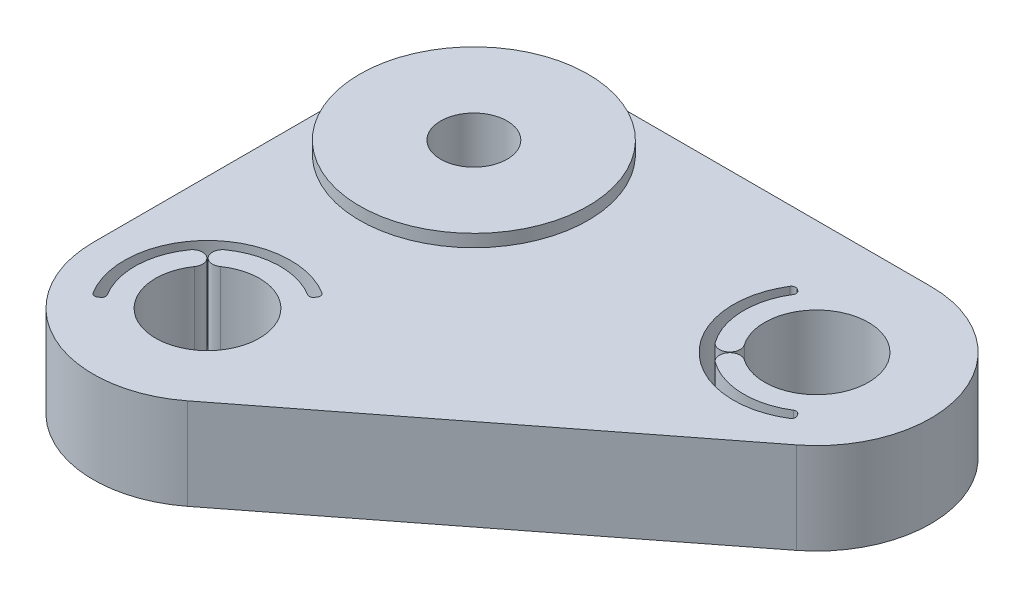
SolidWorks part; units mm, degrees
ref_plane "Front" through (0, 0, 0) normal (0, 0, 1) x (1, 0, 0)
ref_plane "Top" through (0, 0, 0) normal (0, 1, 0) x (1, 0, 0)
ref_plane "Right" through (0, 0, 0) normal (1, 0, 0) x (0, 0, -1)
sketch "Sketch2" plane through (0, 0, 0) normal (0, 1, 0) x (1, 0, 0)
  line L0 (0, 0) -> (0, 12.825) construction
  line L1 (0, 12.825) -> (16.5, 12.825) construction
  line L2 (-5.5, -11.241) -> (32.5382, 18.325) construction
  line L3 (32.5382, 18.325) -> (-5.5, 18.325) construction
  line L4 (-5.5, 18.325) -> (-5.5, -11.241) construction
  line L5 (-5.5, 0) -> (-5.5, 12.825)
  line L6 (0, 18.325) -> (16.5, 18.325)
  line L7 (19.8753, 8.4825) -> (3.3753, -4.3425)
  circle A0 centre (0, 12.825) radius 1.6
  circle A1 centre (16.5, 12.825) radius 2.5
  circle A2 centre (0, 0) radius 2.5
  circle A3 centre (16.5, 12.825) radius 5.5 construction
  circle A4 centre (0, 12.825) radius 5.5 construction
  circle A5 centre (0, 0) radius 5.5 construction
  arc A6 (-5.5, 12.825) -> (0, 18.325) centre (0, 12.825) cw
  arc A7 (16.5, 18.325) -> (19.8753, 8.4825) centre (16.5, 12.825) cw
  arc A8 (3.3753, -4.3425) -> (-5.5, 0) centre (0, 0) cw
  dimension "D3" = 5
  dimension "D4" = 3.2
  dimension "D5" = 3
  dimension "D1" = 12.825
  dimension "D2" = 16.5
extrude "Boss-Extrude1" add sketch "Sketch2" along normal blind 1.57
other "Move Face1" [suppressed] offset 0.0762 parameters "D1"=0.0762
sketch "Sketch3" plane through (0, 1.57, 0) normal (0, 1, 0) x (1, 0, 0)
  line L3 (3.3753, -4.3425) -> (19.8753, 8.4825)
  line L4 (16.5, 18.325) -> (0, 18.325)
  line L5 (-5.5, 12.825) -> (-5.5, 0)
  line L6 (3.3753, -4.3425) -> (19.8753, 8.4825)
  line L7 (16.5, 18.325) -> (0, 18.325)
  line L8 (-5.5, 12.825) -> (-5.5, 0)
  circle A0 centre (0, 0) radius 2.5 construction
  circle A1 centre (16.5, 12.825) radius 2.5 construction
  circle A2 centre (0, 12.825) radius 1.6 construction
  arc A3 (-5.5, 0) -> (3.3753, -4.3425) centre (0, 0) ccw
  arc A4 (19.8753, 8.4825) -> (16.5, 18.325) centre (16.5, 12.825) ccw
  arc A5 (0, 18.325) -> (-5.5, 12.825) centre (0, 12.825) ccw
  arc A6 (-5.5, 0) -> (3.3753, -4.3425) centre (0, 0) ccw
  arc A7 (19.8753, 8.4825) -> (16.5, 18.325) centre (16.5, 12.825) ccw
  arc A8 (0, 18.325) -> (-5.5, 12.825) centre (0, 12.825) ccw
  circle A9 centre (0, 0) radius 2.5
  circle A10 centre (16.5, 12.825) radius 2.5
  circle A11 centre (0, 12.825) radius 1.6
  dimension "D1" = 0
extrude "Boss-Extrude2" add sketch "Sketch3" along normal blind 2.83
sketch "Sketch4" plane through (0, 4.4, 0) normal (0, 1, 0) x (1, 0, 0)
  circle A8 centre (0, 12.825) radius 1.6 construction
  circle A9 centre (0, 12.825) radius 1.6
  circle A10 centre (0, 12.825) radius 5.5
  arc A11 (0, 18.325) -> (-5.5, 12.825) centre (0, 12.825) ccw construction
extrude "Boss-Extrude3" add sketch "Sketch4" along normal blind 0.6
sketch "Sketch5" plane through (0, 0, 0) normal (0, -1, 0) x (1, 0, 0)
  line B0 (13.4736, -14.9441) -> (13.3915, -15.0016)
  line B1 (18.6191, -9.7986) -> (18.6766, -9.7165)
  line B2 (14.0425, -11.1043) -> (16.5, -12.825) construction
  arc B3 (13.1072, -14.9437) -> (18.6187, -9.4322) centre (16.5, -12.825) cw
  arc B4 (14.4521, -11.3911) -> (13.633, -10.8175) centre (14.0425, -11.1043) ccw
  arc B5 (13.633, -10.8175) -> (13.5286, -14.6746) centre (16.5, -12.825) ccw
  arc B6 (14.4925, -9.958) -> (18.3496, -9.8536) centre (16.5, -12.825) cw
  arc B7 (15.0661, -10.7771) -> (14.4925, -9.958) centre (14.7793, -10.3675) cw
  arc B8 (14.4521, -11.3911) -> (15.0661, -10.7771) centre (16.5, -12.825) cw
  arc B9 (13.4736, -14.9441) -> (13.5286, -14.6746) centre (13.3589, -14.7803) ccw
  arc B10 (13.3915, -15.0016) -> (13.1072, -14.9437) centre (13.2768, -14.8377) cw
  arc B11 (18.6766, -9.7165) -> (18.6187, -9.4322) centre (18.5127, -9.6018) ccw
  arc B12 (18.6191, -9.7986) -> (18.3496, -9.8536) centre (18.4553, -9.6839) cw
  line B13 (0, 0) -> (-2.8284, -2.8284) construction
  line B14 (2.1191, -3.0264) -> (2.1766, -3.1085)
  line B15 (-3.0264, 2.1191) -> (-3.1085, 2.1766)
  line B16 (-1.7207, -2.4575) -> (0, 0) construction
  arc B17 (2.1187, -3.3928) -> (-3.3928, 2.1187) centre (0, 0) cw
  arc B18 (-1.4339, -2.0479) -> (-2.0075, -2.867) centre (-1.7207, -2.4575) ccw
  arc B19 (-2.0075, -2.867) -> (1.8496, -2.9714) centre (0, 0) ccw
  arc B20 (-2.867, -2.0075) -> (-2.9714, 1.8496) centre (0, 0) cw
  arc B21 (-2.0479, -1.4339) -> (-2.867, -2.0075) centre (-2.4575, -1.7207) cw
  arc B22 (-1.4339, -2.0479) -> (-2.0479, -1.4339) centre (0, 0) cw
  arc B23 (2.1191, -3.0264) -> (1.8496, -2.9714) centre (1.9553, -3.1411) ccw
  arc B24 (2.1766, -3.1085) -> (2.1187, -3.3928) centre (2.0127, -3.2232) cw
  arc B25 (-3.1085, 2.1766) -> (-3.3928, 2.1187) centre (-3.2232, 2.0127) ccw
  arc B26 (-3.0264, 2.1191) -> (-2.9714, 1.8496) centre (-3.1411, 1.9553) cw
sketch_block_instance "5mm_bore_flexure_relief-1"
sketch_block "5mm_bore_flexure_relief" parameters "D4"=2.5, "D6"=0.2, "D1"=80, "D2"=0.5, "D3"=70, "D5"=1
sketch_block_instance "5mm_bore_flexure_relief-2"
extrude "bore relief" cut sketch "Sketch5" against normal through all
sketch "Sketch6" plane through (0, 0, -18.325) normal (0, 0, -1) x (-1, 0, 0)
  line L0 (0, 3.8) -> (-16.5, 3.8) construction
  line L1 (0, 4.4) -> (0, 0) construction
  line L2 (-16.5, 4.4) -> (-16.5, 0) construction
  line L3 (-16.5, 4.4) -> (0, 4.4) construction
  text T0 "RXR-01" font "Century Gothic" height in points 12
  dimension "D1" = 0.6
extrude "Part Num Right" cut sketch "Sketch6" against normal blind 0.4
mirror "Mirror3" [suppressed] of bodies 106 104
delete or keep bodies "Body-Delete/Keep 1" [suppressed] type keep bodies bodies 105
sketch "Sketch7" [suppressed] plane through (0, 0, -18.325) normal (0, 0, -1) x (-1, 0, 0)
  line L0 (27.5, 3.8) -> (11, 3.8) construction
  line L1 (27.5, 4.4) -> (27.5, 0) construction
  line L2 (11, 4.4) -> (11, 0) construction
  line L3 (27.5, 4.4) -> (11, 4.4) construction
  text T0 "LXR-01" font "Century Gothic" height in points 12
  dimension "D1" = 0.6
extrude "Part Num Left" [suppressed] cut sketch "Sketch7" against normal blind 0.4
